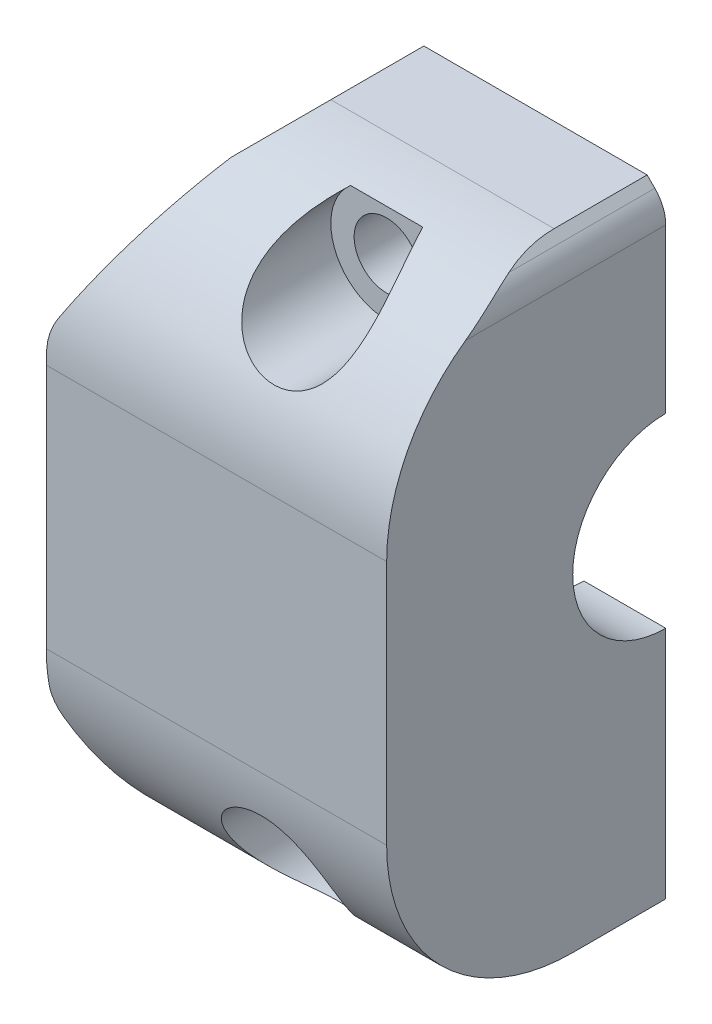
SolidWorks part; units mm, degrees
ref_plane "Front Plane" through (0, 0, 0) normal (0, 0, 1) x (1, 0, 0)
ref_plane "Top Plane" through (0, 0, 0) normal (0, 1, 0) x (1, 0, 0)
ref_plane "Right Plane" through (0, 0, 0) normal (1, 0, 0) x (0, 0, -1)
sketch "Sketch1" plane through (0, 0, 0) normal (0, 0, 1) x (1, 0, 0)
  line L0 (-110.6, 5) -> (-110.6, -5)
  line L1 (-124.6, 14.6) -> (-128.4934, 7.8564) construction
  line L2 (-124.6, 14.6) -> (-128.4934, 7.8564)
  line L3 (-110.6, -17.6) -> (-110.6, -5) construction
  line L4 (-110.6, -17.6) -> (-124.6, -17.6) construction
  line L5 (-128.4934, -10.8564) -> (-124.6, -17.6) construction
  line L6 (-128.8953, 6.3564) -> (-128.8953, -9.3564) construction
  line L7 (-110.6, -17.6) -> (-110.6, -5)
  line L8 (-110.6, -17.6) -> (-124.6, -17.6)
  line L9 (-128.4934, -10.8564) -> (-124.6, -17.6)
  line L10 (-128.8953, 6.3564) -> (-128.8953, -9.3564)
  line L16 (-124.6, -14.6) -> (-123.6, -15.6)
  line L17 (-123.6, -15.6) -> (-111.6, -15.6)
  line L18 (-111.6, -15.6) -> (-111.1858, -15.1858)
  line L19 (-110.6, -13.7716) -> (-110.6, -5)
  line L20 (-110.6, -5) -> (-115, -5)
  line L21 (-115, -5) -> (-115, -10.1)
  line L22 (-115, -10.1) -> (-120.2, -10.1)
  line L23 (-120.2, -10.1) -> (-120.2, 10.1)
  line L24 (-120.2, 10.1) -> (-115, 10.1)
  line L25 (-115, 10.1) -> (-115, 5)
  line L26 (-115, 5) -> (-110.6, 5)
  line L27 (-110.6, 5) -> (-110.6, 13.7716)
  line L28 (-111.1858, 15.1858) -> (-111.6, 15.6)
  line L29 (-111.6, 15.6) -> (-123.6, 15.6)
  line L30 (-123.6, 15.6) -> (-124.6, 14.6)
  line L31 (-124.6, 14.6) -> (-124.6, -14.6)
  line L35 (-110.6, -13.7716) -> (-110.6, -5)
  line L36 (-110.6, -5) -> (-115, -5) construction
  line L37 (-115, -5) -> (-115, -10.1) construction
  line L38 (-115, -10.1) -> (-120.2, -10.1) construction
  line L39 (-120.2, -10.1) -> (-120.2, 10.1) construction
  line L40 (-120.2, 10.1) -> (-115, 10.1) construction
  line L41 (-115, 10.1) -> (-115, 5) construction
  line L42 (-115, 5) -> (-110.6, 5) construction
  line L43 (-110.6, 5) -> (-110.6, 13.7716)
  line L44 (-111.1858, 15.1858) -> (-111.6, 15.6)
  line L45 (-111.6, 15.6) -> (-123.6, 15.6)
  line L46 (-123.6, 15.6) -> (-124.6, 14.6)
  arc A0 (-128.8953, -9.3564) -> (-128.4934, -10.8564) centre (-125.8953, -9.3564) ccw construction
  arc A1 (-128.4934, 7.8564) -> (-128.8953, 6.3564) centre (-125.8953, 6.3564) ccw construction
  arc A2 (-111.1858, -15.1858) -> (-110.6, -13.7716) centre (-112.6, -13.7716) ccw
  arc A3 (-110.6, 13.7716) -> (-111.1858, 15.1858) centre (-112.6, 13.7716) ccw
  arc A5 (-110.6, 13.7716) -> (-111.1858, 15.1858) centre (-112.6, 13.7716) ccw
  arc A6 (-128.8953, -9.3564) -> (-128.4934, -10.8564) centre (-125.8953, -9.3564) ccw
  arc A7 (-128.4934, 7.8564) -> (-128.8953, 6.3564) centre (-125.8953, 6.3564) ccw
  dimension "D1" = 0
extrude "Boss-Extrude1" add sketch "Sketch1" along normal blind 15 contours L2 A7 L10 A6 L9 L8 L7 L0 L43 A5 L44 L45 L46 region at (-116.1829, 0, 0) region at (-112.8, 5.342, 0) region at (-124.6065, -4.7343, 0)
sketch "Sketch3" plane through (-110.6, 0, 0) normal (1, 0, 0) x (0, 0, -1)
  circle A0 centre (0, 0) radius 5
  dimension "D1" = 10
extrude "Cut-Extrude1" cut sketch "Sketch3" against normal blind 13
sketch "Sketch4" plane through (-110.6, 0, 0) normal (1, 0, 0) x (0, 0, -1)
  circle A0 centre (0, 0) radius 10.1
  dimension "D1" = 20.2
extrude "Cut-Extrude2" cut sketch "Sketch4" against normal mid plane 5.2 from offset 7 offset against normal yes
sketch "Sketch5" plane through (0, 0, 0) normal (0, 0, -1) x (-1, 0, 0)
  line L0 (117.6, 15.6) -> (117.6, -17.6) construction
  line L3 (110.6, -17.6) -> (124.6, -17.6) construction
  line L4 (111.6, 15.6) -> (123.6, 15.6) construction
  circle A0 centre (117.6, 12.85) radius 1.75
  circle A1 centre (117.6, -12.85) radius 1.75
  point P10 (0, 0)
  point P11 (117.6, 15.6)
  point P12 (117.6, -17.6)
  dimension "D1" = 4.75
  dimension "D2" = 2.75
  dimension "D3" = 3.5
extrude "Cut-Extrude3" cut sketch "Sketch5" against normal through all
sketch "Sketch6" plane through (0, 0, 0) normal (0, 0, -1) x (-1, 0, 0)
  circle A0 centre (117.6, 12.85) radius 3
  circle A1 centre (117.6, -12.85) radius 3
  dimension "D1" = 6
extrude "Cut-Extrude4" cut sketch "Sketch6" against normal through all from offset 8 offset against normal yes
fillet "Fillet1" radius 10 2 edges at (-114.0005, 15.6, 15) (-117.6, -17.6, 15)
sketch "Sketch7" plane through (0, 0, 0) normal (0, 0, -1) x (-1, 0, 0)
  line L0 (110.6, 0) -> (128.8953, 0) construction
  line L1 (110.6, 5) -> (110.6, -5) construction
  line L2 (128.8953, 6.3564) -> (128.8953, -9.3564) construction
  line L3 (115, -10.1) -> (115, -5) construction
  line L4 (115, -8.6) -> (124.2, -8.6)
  line L5 (115, -8.6) -> (115, 8.6)
  line L6 (115, 8.6) -> (124.2, 8.6)
  line L7 (126.2, -6.6) -> (126.2, 6.6)
  line L8 (115, -8.6) -> (126.2, 8.6) construction
  line L9 (115, 8.6) -> (126.2, -8.6) construction
  line L10 (120.2, -10.1) -> (115, -10.1) construction
  line L11 (120.2, 10.1) -> (120.2, -10.1) construction
  line L12 (124.2, 8.6) -> (126.2, 6.6)
  line L13 (124.2, -8.6) -> (126.2, -6.6)
  point P7 (120.6, 0)
  point P12 (0, 0)
  dimension "D1" = 1.5
  dimension "D2" = 6
extrude "Cut-Extrude5" cut sketch "Sketch7" against normal blind 8
